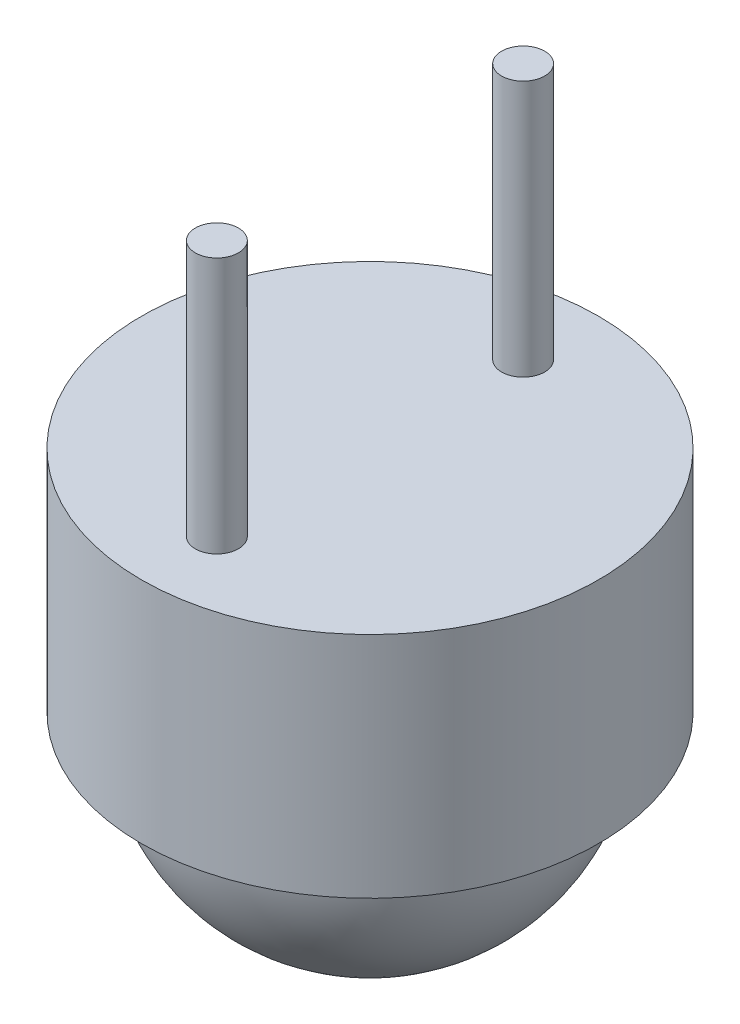
SolidWorks part; units mm, degrees
ref_plane "Front Plane" through (0, 0, 0) normal (0, 0, 1) x (1, 0, 0)
ref_plane "Top Plane" through (0, 0, 0) normal (0, 1, 0) x (1, 0, 0)
ref_plane "Right Plane" through (0, 0, 0) normal (1, 0, 0) x (0, 0, -1)
sketch "Sketch1" plane through (0, 0, 0) normal (0, 0, 1) x (1, 0, 0)
  line L0 (0, -9.525) -> (0, 9.525)
  arc A0 (0, -9.525) -> (0, 9.525) centre (0, 0) ccw
  dimension "D1" = 19.05
revolve "Metal Ball 3/4\"" add sketch "Sketch1" angle 360 about L0
sketch "Sketch2" plane through (0, 0, 0) normal (0, 1, 0) x (1, 0, 0)
  circle A0 centre (0, 0) radius 9.525
  circle A1 centre (0, 0) radius 11.557
  dimension "D1" = 2.032
extrude "Housing Pt. 1" add sketch "Sketch2" along normal blind 9.525 separate body
sketch "Sketch3" plane through (0, 9.525, 0) normal (0, 1, 0) x (1, 0, 0)
  circle A0 centre (0, 0) radius 11.557
  dimension "D1" = 23.114
extrude "Housing Pt. 2" add sketch "Sketch3" along normal blind 2.032
sketch "Sketch4" plane through (0, 11.557, 0) normal (0, 1, 0) x (1, 0, 0)
  line L0 (0, -7.747) -> (0, 7.747) construction
  circle A0 centre (0, 7.747) radius 1.09
  circle A1 centre (0, -7.747) radius 1.09
  point P5 (0, 0)
  dimension "D2" = 2.18
  dimension "D1" = 15.494
extrude "Screw Holes" cut sketch "Sketch4" against normal up to next (2.032 mm away)
sketch "Sketch5" plane through (0, 9.525, 0) normal (0, -1, 0) x (1, 0, 0)
  circle A0 centre (0, 7.747) radius 1.09
  circle A1 centre (0, -7.747) radius 1.09
  dimension "D1" = 2.18
extrude "Screws" add sketch "Sketch5" against normal blind 15 separate body
